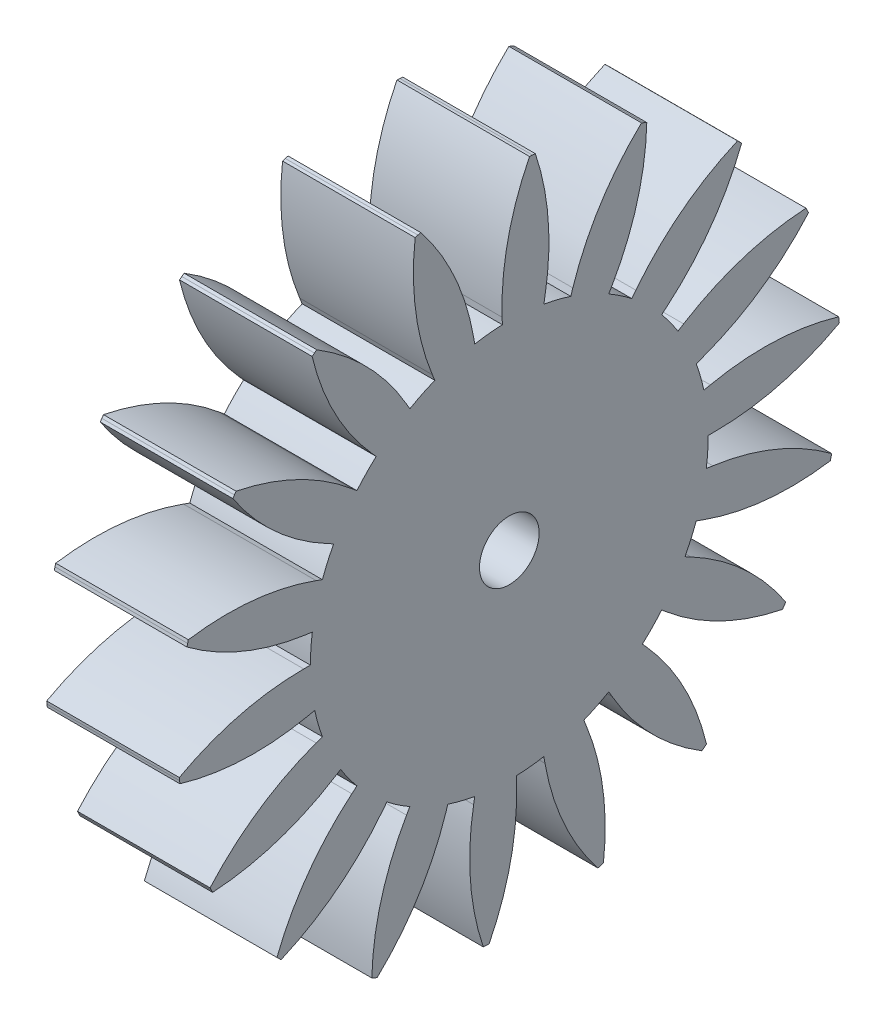
SolidWorks part; units mm, degrees
ref_plane "Front Plane" through (0, 0, 0) normal (0, 0, 1) x (1, 0, 0)
ref_plane "Top Plane" through (0, 0, 0) normal (0, 1, 0) x (1, 0, 0)
ref_plane "Right Plane" through (0, 0, 0) normal (1, 0, 0) x (0, 0, -1)
sketch "Sketch1" plane through (0, 0, 0) normal (1, 0, 0) x (0, 0, -1)
  line L0 (0, 0) -> (40, 0) construction
  line L1 (0, 0) -> (39.8158, 3.8338) construction
  line L2 (0, 0) -> (39.7809, 4.1811) construction
  line L3 (0, 0) -> (39.7429, 4.5281) construction
  line L4 (0, 0) -> (39.1259, 8.3165) construction
  line L5 (15, 0) -> (15.5, 0)
  line L6 (24.8849, 2.3961) -> (24.863, 2.6132)
  line L7 (24.8393, 2.8301) -> (24.863, 2.6132)
  line L8 (14.6722, 3.1187) -> (15.1613, 3.2226)
  line L9 (24.2037, -6.2595) -> (24.2574, -6.048)
  line L10 (24.3092, -5.8361) -> (24.2574, -6.048)
  line L11 (14.0954, -5.1303) -> (14.5652, -5.3013)
  line L12 (14.854, -2.0876) -> (15.3492, -2.1572)
  line L13 (20.6032, -14.1602) -> (20.7259, -13.9798)
  line L14 (20.8471, -13.7984) -> (20.7259, -13.9798)
  line L15 (11.4907, -9.6418) -> (11.8737, -9.9632)
  line L16 (13.2442, -7.0421) -> (13.6857, -7.2768)
  line L17 (14.5176, -20.3529) -> (14.6946, -20.2254)
  line L18 (14.8706, -20.0964) -> (14.6946, -20.2254)
  line L19 (7.5, -12.9904) -> (7.75, -13.4234)
  line L20 (10.037, -11.1472) -> (10.3715, -11.5187)
  line L21 (6.681, -24.0908) -> (6.8909, -24.0315)
  line L22 (7.1004, -23.9705) -> (6.8909, -24.0315)
  line L23 (2.6047, -14.7721) -> (2.6915, -15.2645)
  line L24 (5.6191, -13.9078) -> (5.8064, -14.3713)
  line L25 (-1.9615, -24.9229) -> (-1.7439, -24.9391)
  line L26 (-1.5262, -24.9534) -> (-1.7439, -24.9391)
  line L27 (-2.6047, -14.7721) -> (-2.6915, -15.2645)
  line L28 (0.5235, -14.9909) -> (0.5409, -15.4906)
  line L29 (-10.3673, -22.749) -> (-10.1684, -22.8386)
  line L30 (-9.9687, -22.9265) -> (-10.1684, -22.8386)
  line L31 (-7.5, -12.9904) -> (-7.75, -13.4234)
  line L32 (-4.6353, -14.2658) -> (-4.7898, -14.7414)
  line L33 (-17.5227, -17.8313) -> (-17.3665, -17.9835)
  line L34 (-17.2089, -18.1344) -> (-17.3665, -17.9835)
  line L35 (-11.4907, -9.6418) -> (-11.8737, -9.9632)
  line L36 (-9.2349, -11.8202) -> (-9.5428, -12.2142)
  line L37 (-22.5646, -10.7628) -> (-22.4699, -10.9593)
  line L38 (-22.3734, -11.1549) -> (-22.4699, -10.9593)
  line L39 (-14.0954, -5.1303) -> (-14.5652, -5.3013)
  line L40 (-12.7207, -7.9488) -> (-13.1447, -8.2137)
  line L41 (-24.8849, -2.3961) -> (-24.863, -2.6132)
  line L42 (-24.8393, -2.8301) -> (-24.863, -2.6132)
  line L43 (-15, 0) -> (-15.5, 0)
  line L44 (-14.6722, -3.1187) -> (-15.1613, -3.2226)
  line L45 (-24.2037, 6.2595) -> (-24.2574, 6.048)
  line L46 (-24.3092, 5.8361) -> (-24.2574, 6.048)
  line L47 (-14.0954, 5.1303) -> (-14.5652, 5.3013)
  line L48 (-14.854, 2.0876) -> (-15.3492, 2.1572)
  line L49 (-20.6032, 14.1602) -> (-20.7259, 13.9798)
  line L50 (-20.8471, 13.7984) -> (-20.7259, 13.9798)
  line L51 (-11.4907, 9.6418) -> (-11.8737, 9.9632)
  line L52 (-13.2442, 7.0421) -> (-13.6857, 7.2768)
  line L53 (-14.5176, 20.3529) -> (-14.6946, 20.2254)
  line L54 (-14.8706, 20.0964) -> (-14.6946, 20.2254)
  line L55 (-7.5, 12.9904) -> (-7.75, 13.4234)
  line L56 (-10.037, 11.1472) -> (-10.3715, 11.5187)
  line L57 (-6.681, 24.0908) -> (-6.8909, 24.0315)
  line L58 (-7.1004, 23.9705) -> (-6.8909, 24.0315)
  line L59 (-2.6047, 14.7721) -> (-2.6915, 15.2645)
  line L60 (-5.6191, 13.9078) -> (-5.8064, 14.3713)
  line L61 (1.9615, 24.9229) -> (1.7439, 24.9391)
  line L62 (1.5262, 24.9534) -> (1.7439, 24.9391)
  line L63 (2.6047, 14.7721) -> (2.6915, 15.2645)
  line L64 (-0.5235, 14.9909) -> (-0.5409, 15.4906)
  line L65 (10.3673, 22.749) -> (10.1684, 22.8386)
  line L66 (9.9687, 22.9265) -> (10.1684, 22.8386)
  line L67 (7.5, 12.9904) -> (7.75, 13.4234)
  line L68 (4.6353, 14.2658) -> (4.7898, 14.7414)
  line L69 (17.5227, 17.8313) -> (17.3665, 17.9835)
  line L70 (17.2089, 18.1344) -> (17.3665, 17.9835)
  line L71 (11.4907, 9.6418) -> (11.8737, 9.9632)
  line L72 (9.2349, 11.8202) -> (9.5428, 12.2142)
  line L73 (22.5646, 10.7628) -> (22.4699, 10.9593)
  line L74 (22.3734, 11.1549) -> (22.4699, 10.9593)
  line L75 (14.0954, 5.1303) -> (14.5652, 5.3013)
  line L76 (12.7207, 7.9488) -> (13.1447, 8.2137)
  circle A0 centre (0, 0) radius 2.25
  circle A1 centre (0, 0) radius 15
  circle A2 centre (0, 0) radius 25 construction
  arc A3 (15.5, 0) -> (24.8849, 2.3961) centre (15.5, 19.5769) ccw
  arc A4 (15.1613, 3.2226) -> (24.8393, 2.8301) centre (19.2315, -15.9264) cw
  arc A5 (15.3492, -2.1572) -> (24.3092, -5.8361) centre (12.6246, -21.5435) cw
  arc A6 (14.5652, -5.3013) -> (24.2037, -6.2595) centre (21.2609, 13.0949) ccw
  arc A7 (13.6857, -7.2768) -> (20.8471, -13.7984) centre (4.4949, -24.5622) cw
  arc A8 (11.8737, -9.9632) -> (20.6032, -14.1602) centre (24.4575, 5.0335) ccw
  arc A9 (10.3715, -11.5187) -> (14.8706, -20.0964) centre (-4.1769, -24.6182) cw
  arc A10 (7.75, -13.4234) -> (14.5176, -20.3529) centre (24.7041, -3.635) ccw
  arc A11 (5.8064, -14.3713) -> (7.1004, -23.9705) centre (-12.3449, -21.705) cw
  arc A12 (2.6915, -15.2645) -> (6.681, -24.0908) centre (21.971, -11.865) ccw
  arc A13 (0.5409, -15.4906) -> (-1.5262, -24.9534) centre (-19.024, -16.1738) cw
  arc A14 (-2.6915, -15.2645) -> (-1.9615, -24.9229) centre (16.5879, -18.664) ccw
  arc A15 (-4.7898, -14.7414) -> (-9.9687, -22.9265) centre (-23.4085, -8.6918) cw
  arc A16 (-7.75, -13.4234) -> (-10.3673, -22.749) centre (9.2041, -23.2118) ccw
  arc A17 (-9.5428, -12.2142) -> (-17.2089, -18.1344) centre (-24.9695, -0.1614) cw
  arc A18 (-11.8737, -9.9632) -> (-17.5227, -17.8313) centre (0.7101, -24.96) ccw
  arc A19 (-13.1447, -8.2137) -> (-22.3734, -11.1549) centre (-23.5189, 8.3884) cw
  arc A20 (-14.5652, -5.3013) -> (-22.5646, -10.7628) centre (-7.8696, -23.6975) ccw
  arc A21 (-15.1613, -3.2226) -> (-24.8393, -2.8301) centre (-19.2315, 15.9264) cw
  arc A22 (-15.5, 0) -> (-24.8849, -2.3961) centre (-15.5, -19.5769) ccw
  arc A23 (-15.3492, 2.1572) -> (-24.3092, 5.8361) centre (-12.6246, 21.5435) cw
  arc A24 (-14.5652, 5.3013) -> (-24.2037, 6.2595) centre (-21.2609, -13.0949) ccw
  arc A25 (-13.6857, 7.2768) -> (-20.8471, 13.7984) centre (-4.4949, 24.5622) cw
  arc A26 (-11.8737, 9.9632) -> (-20.6032, 14.1602) centre (-24.4575, -5.0335) ccw
  arc A27 (-10.3715, 11.5187) -> (-14.8706, 20.0964) centre (4.1769, 24.6182) cw
  arc A28 (-7.75, 13.4234) -> (-14.5176, 20.3529) centre (-24.7041, 3.635) ccw
  arc A29 (-5.8064, 14.3713) -> (-7.1004, 23.9705) centre (12.3449, 21.705) cw
  arc A30 (-2.6915, 15.2645) -> (-6.681, 24.0908) centre (-21.971, 11.865) ccw
  arc A31 (-0.5409, 15.4906) -> (1.5262, 24.9534) centre (19.024, 16.1738) cw
  arc A32 (2.6915, 15.2645) -> (1.9615, 24.9229) centre (-16.5879, 18.664) ccw
  arc A33 (4.7898, 14.7414) -> (9.9687, 22.9265) centre (23.4085, 8.6918) cw
  arc A34 (7.75, 13.4234) -> (10.3673, 22.749) centre (-9.2041, 23.2118) ccw
  arc A35 (9.5428, 12.2142) -> (17.2089, 18.1344) centre (24.9695, 0.1614) cw
  arc A36 (11.8737, 9.9632) -> (17.5227, 17.8313) centre (-0.7101, 24.96) ccw
  arc A37 (13.1447, 8.2137) -> (22.3734, 11.1549) centre (23.5189, -8.3884) cw
  arc A38 (14.5652, 5.3013) -> (22.5646, 10.7628) centre (7.8696, 23.6975) ccw
  point P10 (24.4537, 5.1978)
  point P11 (24.8393, 2.8301)
  point P12 (24.863, 2.6132)
  point P13 (24.8849, 2.3961)
  point P14 (15, 0)
  point P19 (24.874, 2.5047)
  point P20 (24.8512, 2.7216)
  point P182 (0, 0)
  dimension "D1" = 4.5
  dimension "D2" = 30
  dimension "D3" = 12
  dimension "D4" = 6
  dimension "D5" = 6.5
  dimension "D6" = 5.5
  dimension "D7" = 40
  dimension "D8" = 10
  dimension "D9" = 0.5
  dimension "D10" = 18
extrude "Boss-Extrude2" add sketch "Sketch1" along normal blind 10 contours L75 A38 L73 L74 A37 L76 A1 | L71 A36 L69 L70 A35 L72 A1 | L67 A34 L65 L66 A33 L68 A1 | L63 A32 L61 L62 A31 L64 A1 | L59 A30 L57 L58 A29 L60 A1 | L55 A28 L53 L54 A27 L56 A1 | L51 A26 L49 L50 A25 L52 A1 | L47 A24 L45 L46 A23 L48 A1 | L43 A22 L41 L42 A21 L44 A1 | L39 A20 L37 L38 A19 L40 A1 | L35 A18 L33 L34 A17 L36 A1 | L31 A16 L29 L30 A15 L32 A1 | L27 A14 L25 L26 A13 L28 A1 | L23 A12 L21 L22 A11 L24 A1 | L19 A10 L17 L18 A9 L20 A1 | L15 A8 L13 L14 A7 L16 A1 | L11 A6 L9 L10 A5 L12 A1 | A4 L8 A1 L5 A3 L6 L7 | A1 A0 region at (0, 2.0024, -19.0518) region at (0, -1.0168, -14.5402) region at (0, -4.6344, -18.5877) region at (0, 8.3978, -17.218) region at (0, -10.7123, -15.8817) region at (0, 13.7802, -13.3074) region at (0, -15.4981, -11.2601) region at (0, 17.5006, -7.7918) region at (0, -18.4147, -5.2803) region at (0, 19.1101, -1.3363) region at (0, -19.1101, 1.3363) region at (0, 18.4147, 5.2803) region at (0, -17.5006, 7.7918) region at (0, 15.4981, 11.2601) region at (0, -13.7802, 13.3074) region at (0, 10.7123, 15.8817) region at (0, -8.3978, 17.218) region at (0, 4.6344, 18.5877) region at (0, -2.0024, 19.0518)
equation "\"Gear_angle\" = 12"
equation "\"D3@Sketch1\"=\"Gear_angle\""
equation "\"D4@Sketch1\"=\"Gear_angle\"*0.5"
equation "\"D5@Sketch1\"=\"Gear_angle\"*0.5 +0.5"
equation "\"D6@Sketch1\"=\"Gear_angle\"*0.5 -0.5"
equation "\"Gear_diameter\"= 30mm"
equation "\"D2@Sketch1\"=\"Gear_diameter\""
equation "\"Gear_tooth_height\"= 2mm"
equation "\"gear_thickeness\"=10"
